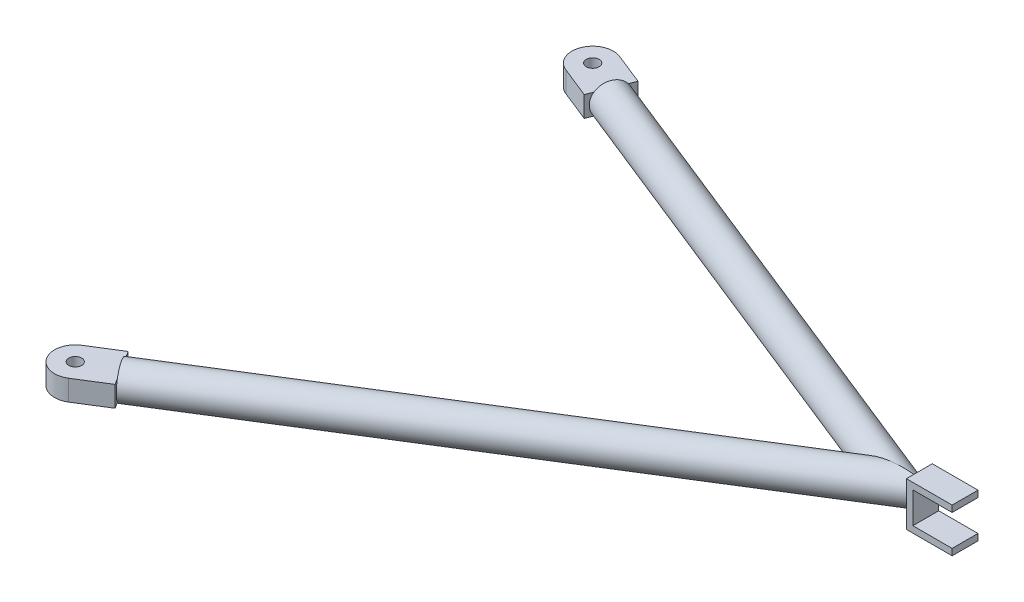
SolidWorks part; units mm, degrees
ref_plane "Front Plane" through (0, 0, 0) normal (0, 0, 1) x (1, 0, 0)
ref_plane "Top Plane" through (0, 0, 0) normal (0, 1, 0) x (1, 0, 0)
ref_plane "Right Plane" through (0, 0, 0) normal (1, 0, 0) x (0, 0, -1)
sketch "Sketch1" plane through (0, 0, 0) normal (0, 1, 0) x (1, 0, 0)
  line L0 (0, 0) -> (-247.6207, 99.06)
  line L1 (0, 0) -> (-247.6207, -154.94)
  line L2 (-247.6207, 99.06) -> (-247.6207, -154.94) construction
  dimension "D1" = 266.7
  dimension "D2" = 292.1
  dimension "D3" = 254
ref_plane "Plane1" through (-247.6207, 0, 154.94) normal (-0.8477, 0, 0.5304) x (0.5304, 0, 0.8477)
sketch "Sketch2" plane through (-247.6207, 0, 154.94) normal (-0.8477, 0, 0.5304) x (0.5304, 0, 0.8477)
  circle A0 centre (0, 0) radius 8.255
  dimension "D1" = 16.51
sweep "Sweep1" add profiles "Sketch2" path "Sketch1"
sketch "Sketch3" plane through (0, 0, 0) normal (0, 0, 1) x (1, 0, 0)
  line L0 (34.2567, -10.795) -> (11.811, -10.795)
  line L1 (11.811, -10.795) -> (11.811, 10.795)
  line L2 (11.811, 10.795) -> (34.2567, 10.795)
  line L3 (34.2567, 10.795) -> (34.2567, 7.62)
  line L4 (34.2567, 7.62) -> (14.986, 7.62)
  line L5 (14.986, 7.62) -> (14.986, -7.62)
  line L6 (14.986, -7.62) -> (34.2567, -7.62)
  line L7 (34.2567, -7.62) -> (34.2567, -10.795)
  line L8 (-18.161, 0) -> (18.161, 0) construction
  ellipse E0 centre (0, 0) end of major axis (18.161, 0) minor radius 8.255 construction
  ellipse E1 centre (0, 0) end of major axis (18.161, 0) minor radius 8.255 construction
  point P21 (11.811, 0)
  dimension "D1" = 3.175
  dimension "D2" = 15.24
  dimension "D3" = 3.175
  dimension "D4" = 6.35
extrude "Boss-Extrude1" add sketch "Sketch3" along normal blind 6.35 and the other way blind 6.35
sketch "Sketch4" plane through (-247.6207, 0, 154.94) normal (-0.8477, 0, 0.5304) x (0.5304, 0, 0.8477)
  line L1 (-10.16, 5.08) -> (10.16, 5.08)
  line L2 (-10.16, 5.08) -> (-10.16, -5.08)
  line L3 (-10.16, -5.08) -> (10.16, -5.08)
  line L4 (10.16, 5.08) -> (10.16, -5.08)
  line L5 (-10.16, 5.08) -> (10.16, -5.08) construction
  line L6 (-10.16, -5.08) -> (10.16, 5.08) construction
  point P0 (0, 0)
  dimension "D1" = 20.32
  dimension "D2" = 10.16
extrude "Boss-Extrude2" add sketch "Sketch4" along normal blind 10.16 and the other way blind 16.51
sketch "Sketch5" plane through (-247.6207, 0, -99.06) normal (-0.9285, 0, -0.3714) x (-0.3714, 0, 0.9285)
  line L1 (-10.16, 5.08) -> (10.16, 5.08)
  line L2 (-10.16, 5.08) -> (-10.16, -5.08)
  line L3 (-10.16, -5.08) -> (10.16, -5.08)
  line L4 (10.16, 5.08) -> (10.16, -5.08)
  line L5 (-10.16, 5.08) -> (10.16, -5.08) construction
  line L6 (-10.16, -5.08) -> (10.16, 5.08) construction
  point P0 (0, 0)
  dimension "D1" = 20.32
  dimension "D2" = 10.16
extrude "Boss-Extrude3" add sketch "Sketch5" along normal blind 10.16 and the other way blind 16.256
sketch "Sketch7" plane through (0, 5.08, 0) normal (0, 1, 0) x (1, 0, 0)
  line L8 (-236.3013, 83.5889) -> (-234.9444, 86.9807)
  line L9 (-234.9444, 86.9807) -> (-250.0375, 93.0187)
  line L10 (-250.0375, 93.0187) -> (-245.2039, 105.1013)
  line L11 (-245.2039, 105.1013) -> (-230.1108, 99.0634)
  line L12 (-230.1108, 99.0634) -> (-228.7539, 102.4552)
  line L13 (-228.7539, 102.4552) -> (-253.2801, 112.2669)
  line L14 (-253.2801, 112.2669) -> (-260.8276, 93.4005)
  line L15 (-260.8276, 93.4005) -> (-236.3013, 83.5889)
  line L22 (-257.0539, 102.8337) -> (-260.8276, 93.4005)
  line L23 (-260.8276, 93.4005) -> (-251.3944, 89.6268)
  arc A0 (-257.0539, 102.8337) -> (-251.3944, 89.6268) centre (-247.6207, 99.06) ccw
  dimension "D1" = 0
extrude "Cut-Extrude1" cut sketch "Sketch7" against normal through all
ref_plane "Plane2" through (0, 0, 0) normal (-0.3714, 0, 0.9285) x (0.9285, 0, 0.3714)
mirror "Mirror1" about plane through (0, 0, 0) normal (-0.3714, 0, 0.9285) of "Cut-Extrude1"
sketch "Sketch9" plane through (0, 5.08, 0) normal (0, 1, 0) x (1, 0, 0)
  line L0 (-239.014, -137.5696) -> (-261.6228, -151.7163) construction
  line L1 (-228.2355, -154.7954) -> (-250.8444, -168.9421) construction
  line L2 (-250.8444, -168.9421) -> (-261.6228, -151.7163) construction
  line L3 (-242.2315, -163.5529) -> (-250.8444, -168.9421)
  line L4 (-250.8444, -168.9421) -> (-256.2336, -160.3292)
  arc A0 (-256.2336, -160.3292) -> (-242.2315, -163.5529) centre (-247.6207, -154.94) ccw
extrude "Cut-Extrude2" cut sketch "Sketch9" against normal through all
ref_plane "Plane3" through (0, 0, 0) normal (0.5304, 0, 0.8477) x (0.8477, 0, -0.5304)
mirror "Mirror2" about plane through (0, 0, 0) normal (0.5304, 0, 0.8477) of "Cut-Extrude2"
sketch "Sketch10" plane through (-247.6207, 0, 154.94) normal (-0.8477, 0, 0.5304) x (0.5304, 0, 0.8477)
  line L0 (6.5068, -5.08) -> (-6.5068, -5.08) construction
  line L1 (-6.5068, 5.08) -> (6.5068, 5.08) construction
  line L2 (6.5068, -5.08) -> (-6.5068, -5.08)
  line L3 (-6.5068, 5.08) -> (6.5068, 5.08)
  arc A0 (-6.5068, -5.08) -> (6.5068, -5.08) centre (0, 0) ccw construction
  arc A1 (6.5068, 5.08) -> (-6.5068, 5.08) centre (0, 0) ccw construction
  arc A2 (-6.5068, -5.08) -> (6.5068, -5.08) centre (0, 0) ccw
  arc A3 (6.5068, 5.08) -> (-6.5068, 5.08) centre (0, 0) ccw
extrude "Cut-Extrude3" cut sketch "Sketch10" against normal up to surface (16.51 mm away) up to face at (-228.9726, 0, 153.6175)
sketch "Sketch11" plane through (-247.6207, 0, -99.06) normal (-0.9285, 0, -0.3714) x (-0.3714, 0, 0.9285)
  line L0 (6.5068, -5.08) -> (-6.5068, -5.08) construction
  line L1 (-6.5068, 5.08) -> (6.5068, 5.08) construction
  line L2 (6.5068, -5.08) -> (-6.5068, -5.08)
  line L3 (-6.5068, 5.08) -> (6.5068, 5.08)
  arc A0 (-6.5068, -5.08) -> (6.5068, -5.08) centre (0, 0) ccw construction
  arc A1 (6.5068, 5.08) -> (-6.5068, 5.08) centre (0, 0) ccw construction
  arc A2 (-6.5068, -5.08) -> (6.5068, -5.08) centre (0, 0) ccw
  arc A3 (6.5068, 5.08) -> (-6.5068, 5.08) centre (0, 0) ccw
extrude "Cut-Extrude4" cut sketch "Sketch11" along direction (0.9285, 0, 0.3714) on the side against the normal up to surface (16.256 mm away) up to face at (-235.7852, 0, -84.879)
sketch "Sketch12" plane through (0, 0, 6.35) normal (0, 0, 1) x (1, 0, 0)
  line L1 (14.986, 4.6631) -> (14.986, -4.6631)
  line L2 (14.986, 4.6631) -> (14.986, -4.6631)
  ellipse E1 centre (0, 0) end of major axis (18.161, 0) minor radius 8.255 (14.986, -4.6631) -> (14.986, 4.6631) ccw
  ellipse E2 centre (0, 0) end of major axis (18.161, 0) minor radius 8.255 (14.986, -4.6631) -> (14.986, 4.6631) ccw
  dimension "D1" = 0
extrude "Cut-Extrude5" cut sketch "Sketch12" against normal through all
sketch "Sketch13" plane through (0, 5.08, 0) normal (0, 1, 0) x (1, 0, 0)
  point P0 (-247.6207, 99.06)
  point P1 (-247.6207, -154.94)
hole_wizard "E (0.25) Diameter Hole1" positions "3DSketch1" profile "Sketch14" hole size "E" standard "ANSI Inch"
sketch3d "3DSketch1"
  point P0 (-247.6207, 5.08, -99.06)
  point P3 (-247.6207, 5.08, 154.94)
sketch "Sketch14" plane through (-247.6207, 5.08, -99.06) normal (1, 0, 0) x (0, 0, 1)
  line L0 (0, 0) -> (0, 20.9577)
  line L1 (0, 20.9577) -> (3.175, 19.05)
  line L2 (3.175, 19.05) -> (3.175, 0)
  line L5 (3.175, 0) -> (0, 0)
  line L10 (0, 20.9577) -> (-3.175, 19.05) construction
  line L11 (0, -6.35) -> (0, 107.95) construction
  dimension "Hole Dia." = 6.35
  dimension "Hole Depth" = 19.05
  dimension "Drill Angle" = 118
